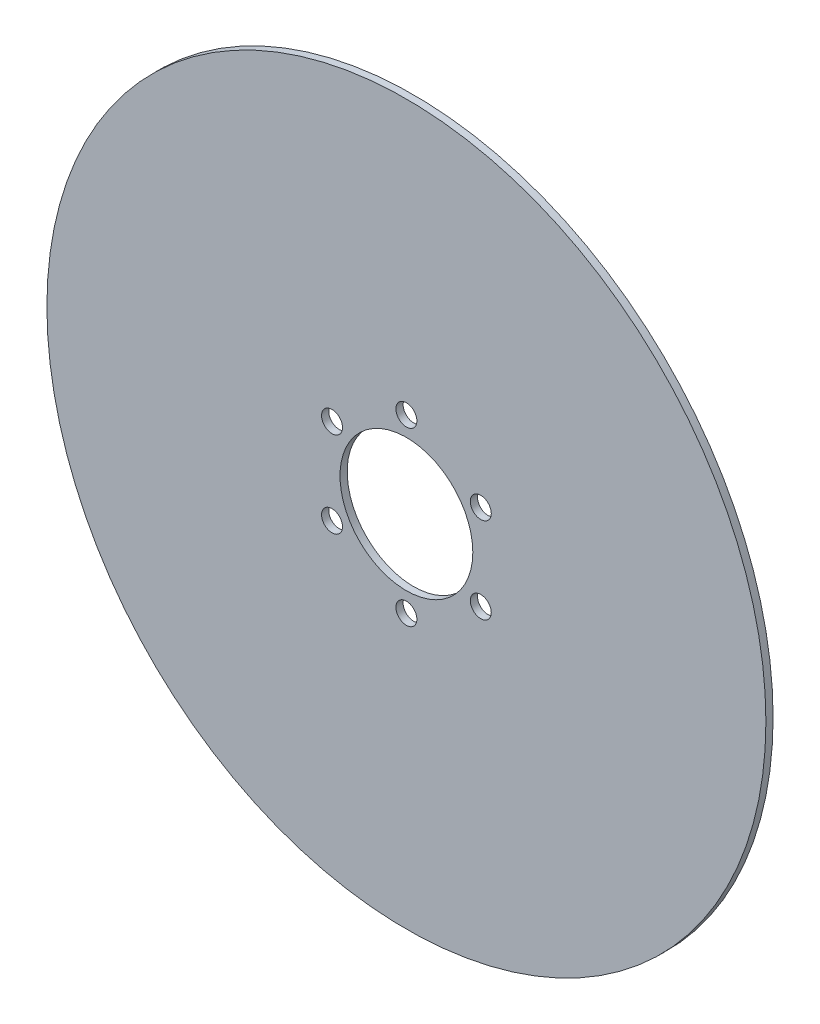
SolidWorks part; units mm, degrees
ref_plane "Front Plane" through (0, 0, 0) normal (0, 0, 1) x (1, 0, 0)
ref_plane "Top Plane" through (0, 0, 0) normal (0, 1, 0) x (1, 0, 0)
ref_plane "Right Plane" through (0, 0, 0) normal (1, 0, 0) x (0, 0, -1)
sketch "Sketch1" plane through (0, 0, 0) normal (0, 0, 1) x (1, 0, 0)
  circle A0 centre (0, 0) radius 90
  circle A1 centre (0, 0) radius 16.625
  circle A2 centre (0, 0) radius 21.5 construction
  circle A3 centre (0, 21.5) radius 2.625
  circle A4 centre (18.6195, 10.75) radius 2.625
  circle A5 centre (18.6195, -10.75) radius 2.625
  circle A6 centre (0, -21.5) radius 2.625
  circle A7 centre (-18.6195, -10.75) radius 2.625
  circle A8 centre (-18.6195, 10.75) radius 2.625
  point P19 (0, 0)
  dimension "D1" = 180
  dimension "D2" = 33.25
  dimension "D3" = 43
  dimension "D4" = 5.25
  dimension "D5" = 6
extrude "Boss-Extrude1" add sketch "Sketch1" along normal blind 0.9 and the other way blind 0.9
